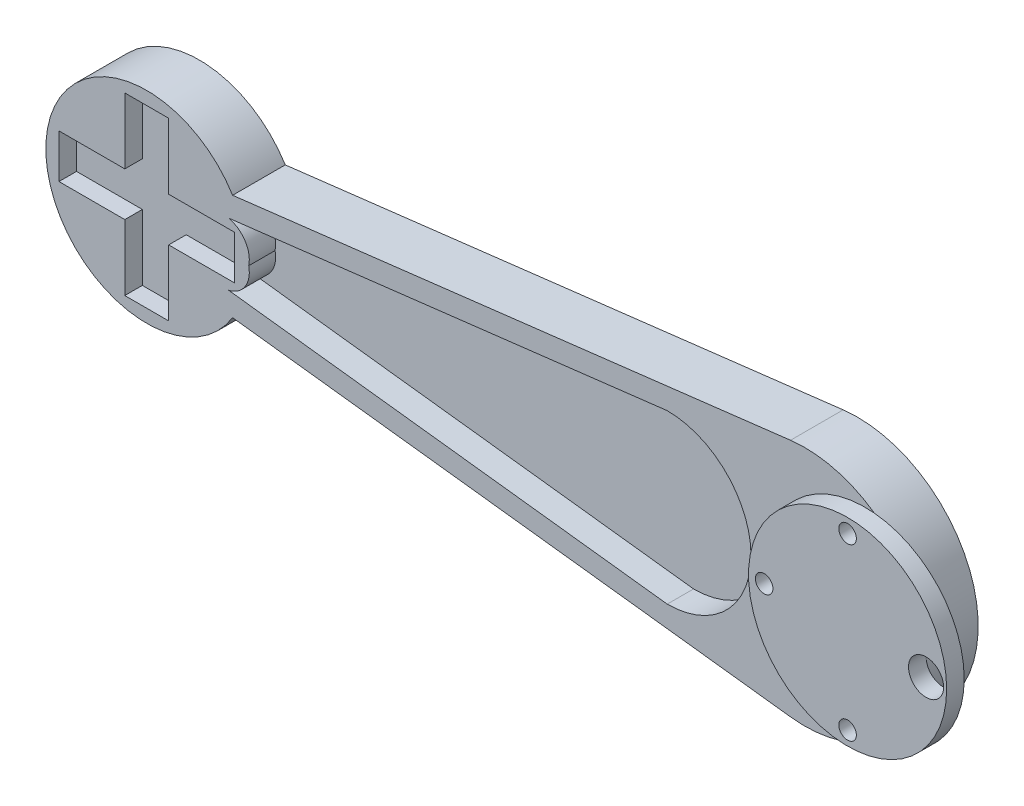
SolidWorks part; units mm, degrees
ref_plane "Front Plane" through (0, 0, 0) normal (0, 0, 1) x (1, 0, 0)
ref_plane "Top Plane" through (0, 0, 0) normal (0, 1, 0) x (1, 0, 0)
ref_plane "Right Plane" through (0, 0, 0) normal (1, 0, 0) x (0, 0, -1)
sketch "Sketch1" plane through (0, 0, 0) normal (0, 0, 1) x (1, 0, 0)
  line L0 (-140.3042, 0) -> (9.6958, 0) construction
  line L1 (6.426, 27.3049) -> (-120.7306, 12.0777)
  line L2 (6.426, -27.3049) -> (-120.7306, -12.0777)
  arc A0 (-120.7306, 12.0777) -> (-120.7306, -12.0777) centre (-140.3042, 0) ccw
  arc A1 (6.426, -27.3049) -> (6.426, 27.3049) centre (9.6958, 0) ccw
  dimension "D1" = 46
  dimension "D3" = 55
  dimension "D2" = 150
extrude "Boss-Extrude1" add sketch "Sketch1" along normal blind 12
sketch "Sketch3" plane through (0, 0, 12) normal (0, 0, 1) x (1, 0, 0)
  line L0 (-121.6703, 7.1224) -> (-21.679, 19.0965)
  line L1 (-120.7306, 12.0777) -> (6.426, 27.3049) construction
  line L2 (-141.2244, 0) -> (0, 0) construction
  line L3 (-121.6703, -7.1224) -> (-21.679, -19.0965)
  arc A0 (-21.679, -19.0965) -> (-21.679, 19.0965) centre (-21.6703, 0) ccw
  arc A1 (-121.6703, 7.1224) -> (-117.0591, 0) centre (-122.9259, 1.2556) cw
  arc A2 (-121.6703, -7.1224) -> (-117.0591, 0) centre (-122.9259, -1.2556) ccw
extrude "Cut-Extrude1" cut sketch "Sketch3" against normal blind 6 contours L3 A0 L0 A1 A2
sketch "Sketch5" plane through (0, 0, 12) normal (0, 0, 1) x (1, 0, 0)
  circle A2 centre (23.4332, 0) radius 22.58
extrude "Boss-Extrude2" add sketch "Sketch5" along normal blind 4
sketch "Sketch6" plane through (0, 0, 16) normal (0, 0, 1) x (1, 0, 0)
  line L0 (23.4332, 22.58) -> (23.4332, -22.58) construction
  line L1 (0.8533, 0) -> (46.0132, 0) construction
  circle A0 centre (23.4332, 0) radius 22.58 construction
  arc A1 (25.5325, 22.4822) -> (25.5325, -22.4822) centre (23.4332, 0) ccw construction
  circle A2 centre (4.4167, 0) radius 2
  circle A3 centre (4.4167, 0) radius 2
  circle A4 centre (4.4167, 0) radius 2
  circle A5 centre (23.4332, -19.3923) radius 2
  circle A6 centre (42.4498, 0) radius 2
  circle A7 centre (23.4332, 19.3923) radius 2
  dimension "D1" = 4
  dimension "D2" = 4
  dimension "D3" = 3.5634
extrude "Cut-Extrude3" cut sketch "Sketch6" against normal blind 16 contours A2
extrude "Cut-Extrude5" cut sketch "Sketch6<3>" against normal blind 16 contours A5 | A6 | A7 region at (23.4332, -19.3923, 16) region at (42.4498, 0, 16)
sketch "Sketch6<3>" plane through (0, 0, 16) normal (0, 0, 1) x (1, 0, 0) same geometry as "Sketch6"
sketch "Sketch8" plane through (0, 0, 16) normal (0, 0, 1) x (1, 0, 0)
  circle A4 centre (41.3186, 0) radius 4
  dimension "D1" = 8
extrude "Cut-Extrude8" cut sketch "Sketch8" against normal through all both and the other way through all
sketch "Sketch10" plane through (0, 0, 12) normal (0, 0, 1) x (1, 0, 0)
  line L0 (-140.3042, 23) -> (-140.3042, 20)
  line L1 (-140.3042, -20) -> (-140.3042, -23)
  line L2 (-145.3042, -20) -> (-135.3042, -20)
  line L3 (-145.3042, -20) -> (-145.3042, -5)
  line L4 (-145.3042, 20) -> (-135.3042, 20)
  line L5 (-135.3042, -20) -> (-135.3042, -5)
  line L8 (-120.3042, -5) -> (-135.3042, -5)
  line L9 (-120.3042, -5) -> (-120.3042, 5)
  line L10 (-120.3042, 5) -> (-135.3042, 5)
  line L11 (-160.3042, -5) -> (-160.3042, 5)
  line L15 (-145.3042, 5) -> (-160.3042, 5)
  line L17 (-145.3042, -5) -> (-160.3042, -5)
  line L18 (-145.3042, 5) -> (-145.3042, 20)
  line L19 (-135.3042, 5) -> (-135.3042, 20)
  arc A0 (-120.7306, 12.0777) -> (-120.7306, -12.0777) centre (-140.3042, 0) ccw construction
  point P6 (-140.3042, 0)
  point P11 (-140.3042, 0)
  dimension "D1" = 40
  dimension "D2" = 40
  dimension "D3" = 10
  dimension "D4" = 10
extrude "Cut-Extrude9" cut sketch "Sketch10" against normal blind 4 contours L10 L19 L4 L18 L15 L11 L17 L3 L2 L5 L8 L9 region at (-140.3042, 0, 12)
